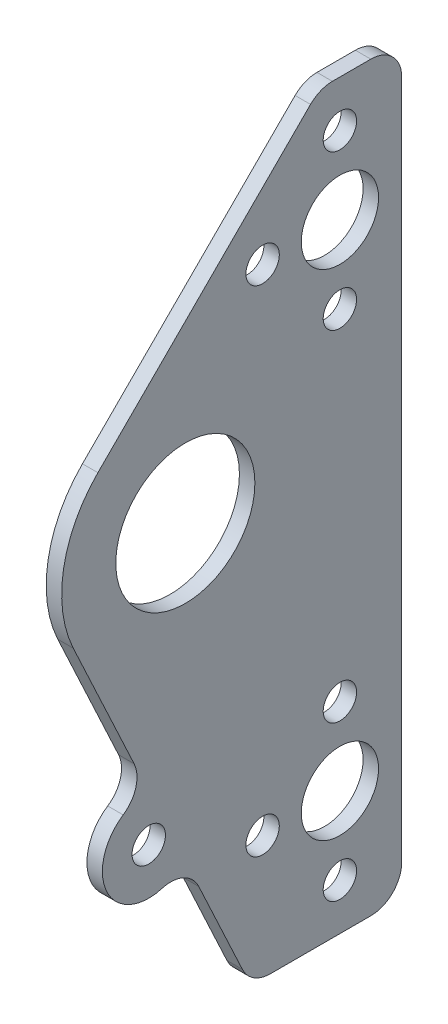
SolidWorks part; units mm, degrees
ref_plane "Front Plane" through (0, 0, 0) normal (0, 0, 1) x (1, 0, 0)
ref_plane "Top Plane" through (0, 0, 0) normal (0, 1, 0) x (1, 0, 0)
ref_plane "Right Plane" through (0, 0, 0) normal (1, 0, 0) x (0, 0, -1)
sketch "Sketch1" plane through (0, 0, 0) normal (1, 0, 0) x (0, 0, -1)
  line L0 (0, 55) -> (0, -55) construction
  line L1 (-19.05, 0) -> (-26.5619, -53.4497) construction
  line L2 (12.7, 38.1) -> (12.7, 53.975) construction
  line L3 (12.7, 38.1) -> (-3.175, 38.1) construction
  line L4 (12.7, -63.5) -> (-3.175, -63.5) construction
  line L5 (25.4, 57.15) -> (25.4, -82.55)
  line L6 (19.05, -88.9) -> (-1.5757, -88.9)
  line L8 (11.1592, 63.5) -> (19.05, 63.5)
  line L9 (55, 0) -> (-55, 0) construction
  line L10 (-37.0105, 17.9605) -> (6.6691, 61.6401)
  line L11 (-42.0702, -10.7345) -> (-29.5744, -37.5319)
  line L12 (-16.3045, -65.9893) -> (-7.3307, -85.2336)
  circle A0 centre (-19.05, 0) radius 14.2875
  circle A1 centre (12.7, 38.1) radius 7.9375
  circle A2 centre (12.7, -63.5) radius 7.9375
  circle A3 centre (-26.5619, -53.4497) radius 3.429
  circle A4 centre (12.7, 38.1) radius 15.875 construction
  circle A6 centre (12.7, 53.975) radius 3.429
  circle A8 centre (12.7, -63.5) radius 15.875 construction
  circle A9 centre (-3.175, -63.5) radius 3.429
  circle A10 centre (12.7, -47.625) radius 3.429
  circle A12 centre (12.7, -79.375) radius 3.429
  arc A14 (25.4, -82.55) -> (19.05, -88.9) centre (19.05, -82.55) cw
  arc A15 (25.4, 57.15) -> (19.05, 63.5) centre (19.05, 57.15) ccw
  circle A17 centre (-3.175, 38.1) radius 3.429
  circle A18 centre (12.7, 22.225) radius 3.429
  circle A19 centre (28.575, -63.5) radius 3.429 [skipped]
  arc A20 (-37.0105, 17.9605) -> (-42.0702, -10.7345) centre (-19.05, 0) ccw
  arc A21 (-31.8224, -45.5092) -> (-23.8605, -62.5836) centre (-26.5619, -53.4497) ccw
  arc A22 (-16.3045, -65.9893) -> (-23.8605, -62.5836) centre (-22.0596, -68.6729) ccw
  arc A23 (-31.8224, -45.5092) -> (-29.5744, -37.5319) centre (-35.3295, -40.2155) ccw
  arc A24 (-7.3307, -85.2336) -> (-1.5757, -88.9) centre (-1.5757, -82.55) ccw
  arc A25 (6.6691, 61.6401) -> (11.1592, 63.5) centre (11.1592, 57.15) cw
  dimension "D1" = 15.875
  dimension "D2" = 28.575
  dimension "D6" = 6.858
  dimension "D8" = 31.75
  dimension "D12" = 4
  dimension "D18" = 19.05
  dimension "D19" = 6.858
  dimension "D15" = 45
  dimension "D23" = 50.8
  dimension "D25" = 6.35
  dimension "D3" = 38.1
  dimension "D4" = 63.5
  dimension "D5" = 53.975
  dimension "D7" = 8
  dimension "D10" = 90
  dimension "D11" = 15.875
  dimension "D13" = 15.875
  dimension "D14" = 25.4
  dimension "D16" = 63.5
  dimension "D17" = 88.9
  dimension "D20" = 12.7
  dimension "D21" = 12.7
  dimension "D22" = 19.05
  dimension "D24" = 65
  dimension "D9" = 3
extrude "Boss-Extrude1" add sketch "Sketch1" along normal blind 3.175
